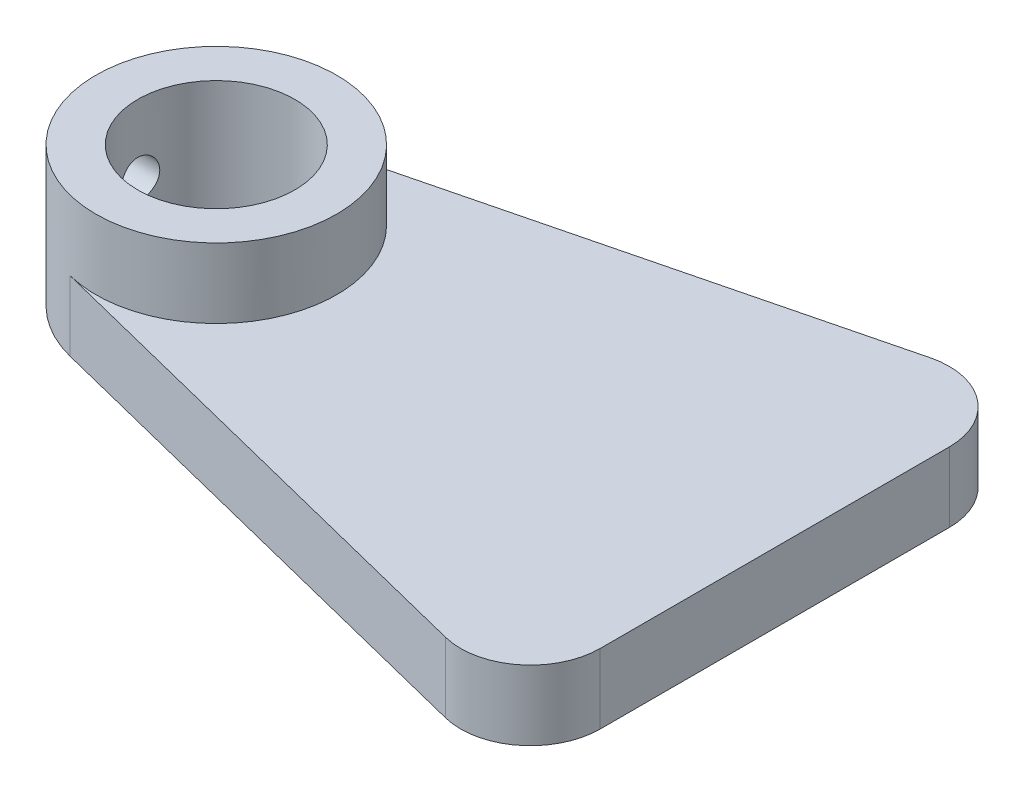
SolidWorks part; units mm, degrees
ref_plane "Front Plane" through (0, 0, 0) normal (0, 0, 1) x (1, 0, 0)
ref_plane "Top Plane" through (0, 0, 0) normal (0, 1, 0) x (1, 0, 0)
ref_plane "Right Plane" through (0, 0, 0) normal (1, 0, 0) x (0, 0, -1)
sketch "Sketch1" plane through (0, 0, 0) normal (0, 1, 0) x (1, 0, 0)
  line L0 (0, 0) -> (35, -12.5) construction
  line L1 (35, -12.5) -> (35, 12.5) construction
  line L2 (35, 12.5) -> (0, 0) construction
  line L3 (-2.0948, 8.3667) -> (33.7856, 17.3503)
  line L4 (40, 12.5) -> (40, -12.5)
  line L5 (0, 0) -> (40, 0) construction
  line L6 (-2.0948, -8.3667) -> (33.7856, -17.3503)
  circle A0 centre (0, 0) radius 5.625
  circle A1 centre (35, 12.5) radius 5
  circle A2 centre (35, -12.5) radius 5
  circle A3 centre (0, 0) radius 8.625
  dimension "D1" = 11.25
  dimension "D2" = 3
  dimension "D5" = 10
  dimension "D3" = 35
  dimension "D4" = 25
extrude "Boss-Extrude1" add sketch "Sketch1" along normal blind 5 contours A3 A0 | A3 L6 A2 L4 A1 L3 | A1 | A2 region at (22.2812, 0, 0) region at (5.1566, 0, -6.6069) region at (35, 0, -12.5) region at (35, 0, 12.5)
extrude "Boss-Extrude2" add sketch "Sketch1<3>" along normal blind 10 contours A3 A0 region at (5.1566, 0, -6.6069)
sketch "Sketch1<3>" plane through (0, 0, 0) normal (0, 1, 0) x (1, 0, 0) same geometry as "Sketch1"
sketch "Sketch2" plane through (0, 0, 0) normal (1, 0, 0) x (0, 0, -1)
  line L0 (12.5, 5) -> (-12.5, 5) construction
  circle A0 centre (0, 5) radius 1.4
  dimension "D1" = 2.8
extrude "Cut-Extrude1" cut sketch "Sketch2" against normal through all
equation "\"m3 hole\"= 3.2"
equation "\"m4 hole\"= 4.2"
equation "\"m5 hole\"= 5.2"
equation "\"m6 hole\"= 6.2"
equation "\"m8 hole\"= 8.2"
equation "\"m3 tapped\"= 2.5"
equation "\"m4 tapped\"= 3.3"
equation "\"m5 tapped\"= 4.2"
equation "\"m6 tapped\"= 5"
equation "\"m8 tapped\"= 6.8"
